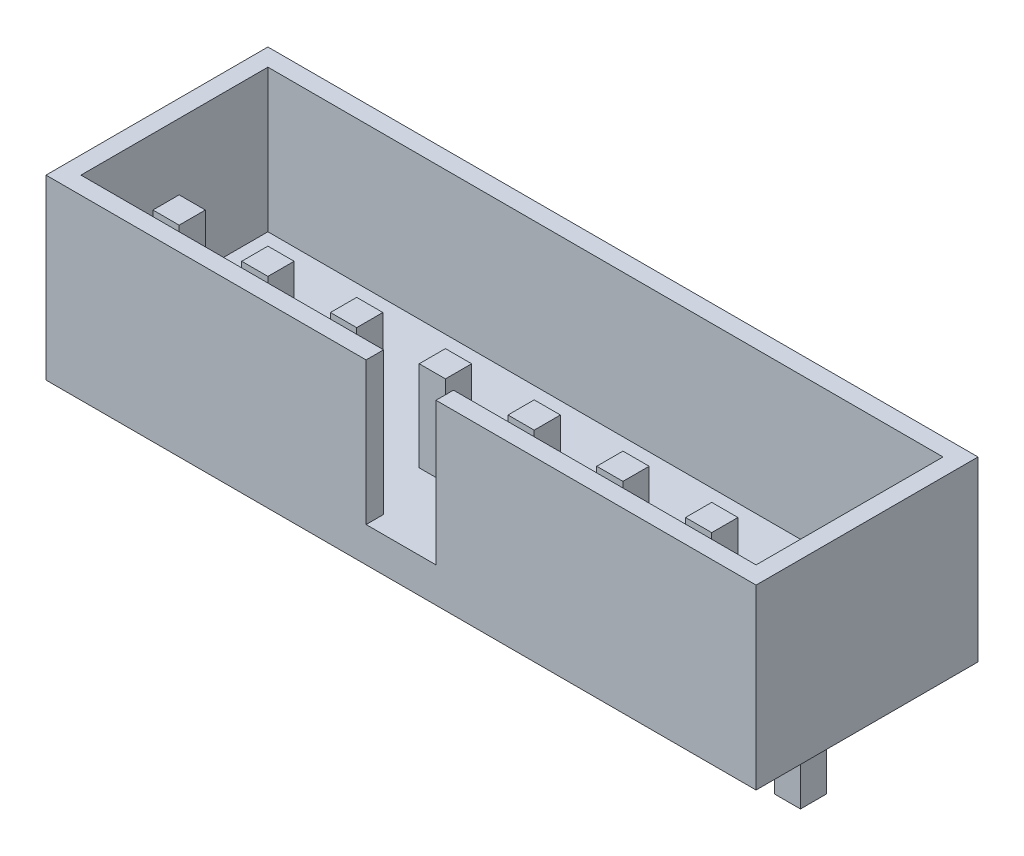
SolidWorks part; units mm, degrees
ref_plane "前视基准面" through (0, 0, 0) normal (0, 0, 1) x (1, 0, 0)
ref_plane "上视基准面" through (0, 0, 0) normal (0, 1, 0) x (1, 0, 0)
ref_plane "右视基准面" through (0, 0, 0) normal (1, 0, 0) x (0, 0, -1)
sketch "草图1" plane through (0, 0, 0) normal (0, 1, 0) x (1, 0, 0)
  line L0 (0, 7.1914) -> (0, -5.4429) construction
  line L1 (-10.16, 3.175) -> (10.16, 3.175)
  line L2 (-10.16, 3.175) -> (-10.16, -3.175)
  line L3 (-10.16, -3.175) -> (10.16, -3.175)
  line L4 (10.16, 3.175) -> (10.16, -3.175)
  line L5 (-10.6234, 0) -> (16.1963, 0) construction
  dimension "D1" = 20.32
  dimension "D2" = 6.35
extrude "拉伸1" add sketch "草图1" along normal blind 5.08
sketch "草图2" plane through (0, 5.08, 0) normal (0, 1, 0) x (-1, 0, 0)
  line L8 (9.66, -2.675) -> (9.66, 2.675)
  line L9 (9.66, 2.675) -> (-9.66, 2.675)
  line L10 (-9.66, 2.675) -> (-9.66, -2.675)
  line L11 (-9.66, -2.675) -> (9.66, -2.675)
  line L12 (9.66, -2.675) -> (9.66, 2.675)
  line L13 (9.66, 2.675) -> (-9.66, 2.675)
  line L14 (-9.66, 2.675) -> (-9.66, -2.675)
  line L15 (-9.66, -2.675) -> (9.66, -2.675)
  dimension "D1" = 0.5
extrude "切除-拉伸1" cut sketch "草图2" against normal offset from surface (4.08 mm away) 1 up to face at (0, 0, 0)
sketch "草图3" plane through (0, 0, 3.175) normal (0, 0, 1) x (1, 0, 0)
  line L0 (-10.16, 5.08) -> (10.16, 5.08) construction
  line L1 (-1, 5.08) -> (1, 5.08)
  line L2 (-1, 5.08) -> (-1, 1)
  line L3 (-1, 1) -> (1, 1)
  line L4 (1, 5.08) -> (1, 1)
  line L5 (9.66, 1) -> (-9.66, 1) construction
  line L6 (0, -1.5083) -> (0, 12.2426) construction
  dimension "D1" = 2
extrude "切除-拉伸2" cut sketch "草图3" against normal blind 1
sketch "草图4" plane through (0, 0, 0) normal (0, -1, 0) x (1, 0, 0)
  line L0 (7.6775, 0.635) -> (-8.5467, 0.635) construction
  line L1 (-10.16, 3.175) -> (10.16, 3.175) construction
  line L2 (0, -3.6953) -> (0, 4.0669) construction
  line L3 (-1.27, 2.1009) -> (-1.27, -0.7012) construction
  line L4 (-1.645, 1.01) -> (-0.895, 1.01)
  line L5 (-1.645, 1.01) -> (-1.645, 0.26)
  line L6 (-1.645, 0.26) -> (-0.895, 0.26)
  line L7 (-0.895, 1.01) -> (-0.895, 0.26)
  line L8 (0.895, 1.01) -> (1.645, 1.01)
  line L9 (0.895, 1.01) -> (0.895, 0.26)
  line L10 (0.895, 0.26) -> (1.645, 0.26)
  line L11 (1.645, 1.01) -> (1.645, 0.26)
  line L12 (2.54, -3.6953) -> (2.54, 4.0669) construction
  line L13 (3.435, 1.01) -> (4.185, 1.01)
  line L14 (3.435, 1.01) -> (3.435, 0.26)
  line L15 (3.435, 0.26) -> (4.185, 0.26)
  line L16 (4.185, 1.01) -> (4.185, 0.26)
  line L17 (5.08, -3.6953) -> (5.08, 4.0669) construction
  line L18 (5.975, 1.01) -> (6.725, 1.01)
  line L19 (5.975, 1.01) -> (5.975, 0.26)
  line L20 (5.975, 0.26) -> (6.725, 0.26)
  line L21 (6.725, 1.01) -> (6.725, 0.26)
  line L22 (7.62, -3.6953) -> (7.62, 4.0669) construction
  line L23 (-4.185, 1.01) -> (-3.435, 1.01)
  line L24 (-4.185, 1.01) -> (-4.185, 0.26)
  line L25 (-4.185, 0.26) -> (-3.435, 0.26)
  line L26 (-3.435, 1.01) -> (-3.435, 0.26)
  line L27 (-3.81, 2.1009) -> (-3.81, -0.7012) construction
  line L28 (5.1375, 0.635) -> (-11.0867, 0.635) construction
  line L29 (-6.725, 1.01) -> (-5.975, 1.01)
  line L30 (-6.725, 1.01) -> (-6.725, 0.26)
  line L31 (-6.725, 0.26) -> (-5.975, 0.26)
  line L32 (-5.975, 1.01) -> (-5.975, 0.26)
  line L33 (-6.35, 2.1009) -> (-6.35, -0.7012) construction
  line L34 (2.5975, 0.635) -> (-13.6267, 0.635) construction
  line L35 (-9.265, 1.01) -> (-8.515, 1.01)
  line L36 (-9.265, 1.01) -> (-9.265, 0.26)
  line L37 (-9.265, 0.26) -> (-8.515, 0.26)
  line L38 (-8.515, 1.01) -> (-8.515, 0.26)
  line L39 (-8.89, 2.1009) -> (-8.89, -0.7012) construction
  line L40 (0.0575, 0.635) -> (-16.1667, 0.635) construction
  line L41 (8.515, 1.01) -> (9.265, 1.01)
  line L42 (8.515, 1.01) -> (8.515, 0.26)
  line L43 (8.515, 0.26) -> (9.265, 0.26)
  line L44 (9.265, 1.01) -> (9.265, 0.26)
  line L45 (10.16, -3.6953) -> (10.16, 4.0669) construction
  dimension "D1" = 2.54
  dimension "D2" = 0.75
  dimension "D3" = 0.75
  dimension "D4" = 1.27
  dimension "D5" = 5
  dimension "D6" = 4
extrude "拉伸2" add sketch "草图4" along normal blind 2 and the other way offset from surface 1.5 other way up to face at (0, 5.08, 0.975)
